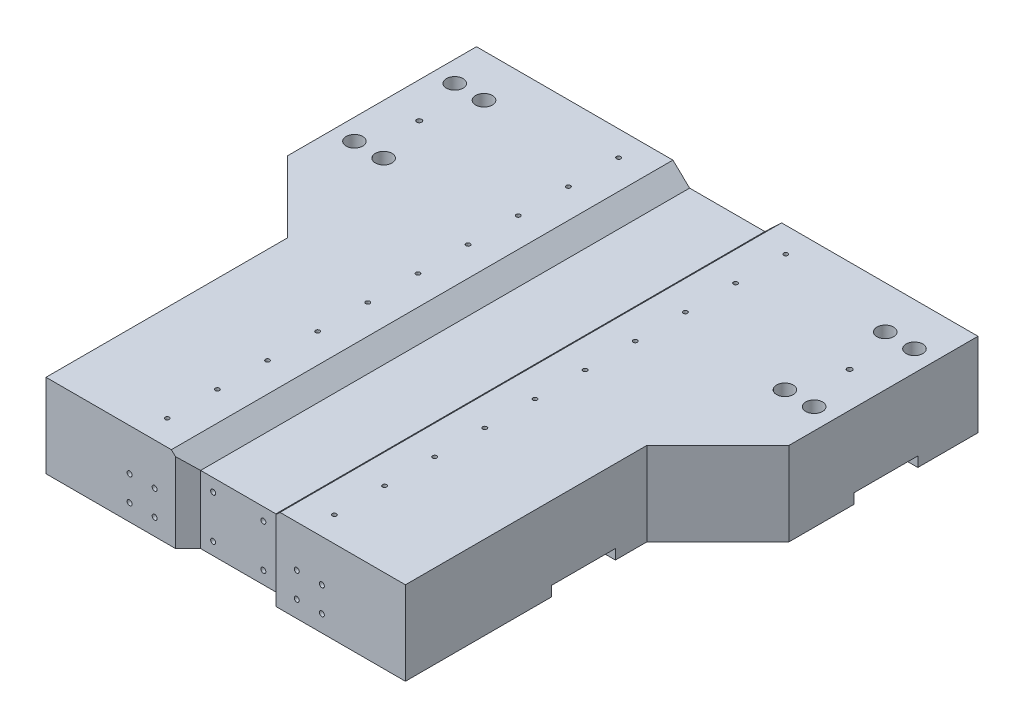
SolidWorks part; units mm, degrees
ref_plane "Front Plane" through (0, 0, 0) normal (0, 0, 1) x (1, 0, 0)
ref_plane "Top Plane" through (0, 0, 0) normal (0, 1, 0) x (1, 0, 0)
ref_plane "Right Plane" through (0, 0, 0) normal (1, 0, 0) x (0, 0, -1)
sketch "Sketch1" plane through (0, 0, 0) normal (0, 1, 0) x (1, 0, 0)
  line L1 (-300, 300) -> (300, 300)
  line L2 (-300, 300) -> (-300, -300)
  line L3 (-300, -300) -> (300, -300)
  line L4 (300, 300) -> (300, -300)
  line L5 (0, -300) -> (0, 300) construction
  line L6 (-300, 0) -> (300, 0) construction
  point P0 (0, 0)
  dimension "D1" = 600
extrude "Boss-Extrude1" add sketch "Sketch1" along normal blind 100
sketch "Sketch2" plane through (0, 100, 0) normal (0, 1, 0) x (1, 0, 0)
  line L0 (-300, -300) -> (-220, -300)
  line L9 (-300, -300) -> (300, -300) construction
  line L11 (300, -300) -> (220, -300)
  line L13 (-300, 300) -> (-300, -300) construction
  line L15 (-300, -300) -> (-300, 60)
  line L16 (300, -300) -> (300, 60)
  line L38 (-300, 60) -> (-300, 74)
  line L41 (300, 60) -> (300, 74)
  line L45 (-220, 74) -> (-300, 74)
  line L48 (220, 74) -> (300, 74)
  line L49 (-220, 74) -> (-215, 74)
  line L50 (-215, 74) -> (-215, -300)
  line L51 (-215, -300) -> (-220, -300)
  line L52 (220, 74) -> (215, 74)
  line L53 (215, 74) -> (215, -300)
  line L54 (215, -300) -> (220, -300)
extrude "Cut-Extrude1" cut sketch "Sketch2" against normal through all
chamfer "Chamfer5" distance 85 angle 45 2 edges at (-215, 50, -74) (215, 50, -74)
sketch "Sketch3" plane through (0, 0, 300) normal (0, 0, 1) x (1, 0, 0)
  line L0 (-35, 81) -> (-45, 81)
  line L2 (35, 81) -> (45, 81)
  line L4 (0, 81) -> (35, 81)
  line L8 (0, 81) -> (-35, 81)
  line L10 (-45, 100) -> (45, 100)
  line L13 (-215, 100) -> (215, 100) construction
  line L14 (-65, 100) -> (-45, 100)
  line L17 (45, 100) -> (65, 100)
  line L22 (-45, 81) -> (-65, 100)
  line L23 (45, 81) -> (65, 100)
extrude "Cut-Extrude2" cut sketch "Sketch3" against normal through all
sketch "Sketch9" plane through (0, 100, 0) normal (0, 1, 0) x (1, 0, 0)
  circle A0 centre (275, 129) radius 10
  circle A1 centre (240, 129) radius 10
  circle A3 centre (240, 249) radius 10
  circle A5 centre (275, 249) radius 10
  circle A6 centre (-275, 129) radius 10
  circle A7 centre (-240, 249) radius 10
  circle A8 centre (-275, 249) radius 10
  circle A11 centre (-240, 129) radius 10
  circle A12 centre (240, 189) radius 10 [skipped]
  circle A13 centre (275, 189) radius 10 [skipped]
  dimension "D1" = 2
  dimension "D2" = 3
extrude "Cut-Extrude5" cut sketch "Sketch9" against normal through all
sketch "Sketch12" plane through (0, 100, 0) normal (0, 1, 0) x (1, 0, 0)
  circle A40 centre (-100, -270) radius 2.5
  circle A41 centre (100, -270) radius 2.5
  circle A42 centre (100, -210) radius 2.5
  circle A43 centre (100, -150) radius 2.5
  circle A44 centre (100, -90) radius 2.5
  circle A45 centre (100, -30) radius 2.5
  circle A46 centre (100, 30) radius 2.5
  circle A47 centre (100, 90) radius 2.5
  circle A48 centre (100, 150) radius 2.5
  circle A49 centre (100, 210) radius 2.5
  circle A50 centre (100, 270) radius 2.5
  circle A61 centre (-100, -210) radius 2.5
  circle A62 centre (-100, -150) radius 2.5
  circle A63 centre (-100, -90) radius 2.5
  circle A64 centre (-100, -30) radius 2.5
  circle A65 centre (-100, 30) radius 2.5
  circle A66 centre (-100, 90) radius 2.5
  circle A67 centre (-100, 150) radius 2.5
  circle A68 centre (-100, 210) radius 2.5
  circle A69 centre (-100, 270) radius 2.5
  dimension "D1" = 2
  dimension "D2" = 10
extrude "Cut-Extrude7" cut sketch "Sketch12" against normal blind 30
sketch "Sketch14" plane through (0, 81, 0) normal (0, 1, 0) x (1, 0, 0)
  line L5 (-45, -300) -> (45, -300)
  line L6 (-45, -300) -> (-45, -285)
  line L11 (45, -285) -> (45, -300)
  line L15 (-45, -285) -> (45, -285)
extrude "Cut-Extrude8" cut sketch "Sketch14" against normal through all
chamfer "Chamfer3" distance 15 angle 45 2 edges at (45, 40.5, 300) (-45, 40.5, 300)
sketch "Sketch15" plane through (-300, 0, 0) normal (-1, 0, 0) x (0, 0, 1)
  line L0 (125, -0.7) -> (125, 12) construction
  line L1 (125, 12) -> (48.8, 12) construction
  line L2 (48.8, 12) -> (48.8, -0.7) construction
  line L3 (48.8, -0.7) -> (125, -0.7) construction
  line L4 (-228, 12) -> (-228, -0.7) construction
  line L5 (-228, -0.7) -> (-151.8, -0.7) construction
  line L6 (-151.8, -0.7) -> (-151.8, 12) construction
  line L7 (-151.8, 12) -> (-228, 12) construction
  line L8 (125, -0.7) -> (125, 12)
  line L9 (125, 12) -> (48.8, 12)
  line L10 (48.8, 12) -> (48.8, -0.7)
  line L11 (48.8, -0.7) -> (125, -0.7)
  line L12 (-228, 12) -> (-228, -0.7)
  line L13 (-228, -0.7) -> (-151.8, -0.7)
  line L14 (-151.8, -0.7) -> (-151.8, 12)
  line L15 (-151.8, 12) -> (-228, 12)
extrude "Cut-Extrude9" cut sketch "Sketch15" against normal through all
sketch "Sketch22" plane through (0, 0, -300) normal (0, 0, -1) x (-1, 0, 0)
  line L0 (-45, 81) -> (-45, 0)
  line L1 (-300, 0) -> (300, 0) construction
  line L2 (-45, 0) -> (45, 0)
  line L3 (45, 0) -> (45, 81)
  line L4 (45, 81) -> (-45, 81)
sketch "Sketch17" plane through (0, 0, 285) normal (0, 0, 1) x (1, 0, 0)
  line L8 (30, 66) -> (-30, 66)
  line L9 (-30, 66) -> (-30, 15)
  line L10 (-30, 15) -> (30, 15)
  line L11 (30, 15) -> (30, 66)
  line L12 (30, 66) -> (-30, 66)
  line L13 (-30, 66) -> (-30, 15)
  line L14 (-30, 15) -> (30, 15)
  line L15 (30, 15) -> (30, 66)
  dimension "D1" = 15
sketch "Sketch19" plane through (0, 0, -300) normal (0, 0, -1) x (-1, 0, 0)
  line L0 (30, 66) -> (30, 15) construction
  line L1 (30, 15) -> (-30, 15) construction
  line L2 (-30, 15) -> (-30, 66) construction
  line L3 (-30, 66) -> (30, 66) construction
  line L4 (30, 66) -> (30, 15)
  line L5 (30, 15) -> (-30, 15)
  line L6 (-30, 15) -> (-30, 66)
  line L7 (-30, 66) -> (30, 66)
sketch "Sketch20" plane through (0, 0, 300) normal (0, 0, 1) x (1, 0, 0)
  line L2 (85, 100) -> (85, 50)
  line L3 (-85, 0) -> (-85, 20)
  line L4 (-215, 100) -> (-65, 100) construction
  line L5 (-85, 100) -> (-85, 50)
  line L6 (115, 100) -> (115, 50)
  line L7 (-115, 100) -> (-115, 50)
  line L8 (0, 34.1921) -> (0, 91.6213)
  line L9 (-215, 0) -> (-60, 0) construction
  line L10 (-115, 0) -> (-115, 20)
  line L11 (85, 0) -> (85, 20)
  line L12 (115, 0) -> (115, 20)
sketch "Sketch21" plane through (0, 0, -300) normal (0, 0, -1) x (-1, 0, 0)
  line L4 (-115, 100) -> (-115, 80)
  line L5 (-85, 100) -> (-85, 80)
  line L6 (85, 100) -> (85, 80)
  line L7 (115, 100) -> (115, 80)
  line L8 (115, 0) -> (115, 20) construction
  line L9 (85, 0) -> (85, 20) construction
  line L10 (-85, 0) -> (-85, 20) construction
  line L11 (-115, 0) -> (-115, 20) construction
  line L12 (115, 0) -> (115, 20)
  line L13 (85, 0) -> (85, 20)
  line L14 (-85, 0) -> (-85, 20)
  line L15 (-115, 0) -> (-115, 20)
hole_wizard "Ø6.0mm Dowel Hole1" positions "3DSketch2" profile "Sketch18" hole size "Ø6.0" standard "ANSI Metric"
sketch3d "3DSketch2"
  point P0 (-30, 66, 285)
  point P3 (30, 66, 285)
  point P6 (30, 15, 285)
  point P9 (-30, 15, 285)
  point P13 (30, 66, -300)
  point P16 (-30, 66, -300)
  point P19 (-30, 15, -300)
  point P22 (30, 15, -300)
  point P26 (-85, 50, 300)
  point P29 (-115, 50, 300)
  point P32 (85, 50, 300)
  point P35 (115, 50, 300)
  point P38 (-115, 80, -300)
  point P41 (-85, 80, -300)
  point P44 (85, 80, -300)
  point P47 (115, 80, -300)
  point P50 (-115, 20, 300)
  point P53 (-85, 20, 300)
  point P56 (85, 20, 300)
  point P59 (115, 20, 300)
  point P62 (-115, 20, -300)
  point P65 (-85, 20, -300)
  point P68 (85, 20, -300)
  point P71 (115, 20, -300)
sketch "Sketch18" plane through (-30, 66, 285) normal (1, 0, 0) x (0, -1, 0)
  line L0 (0, 0) -> (0, 31.8026)
  line L1 (0, 31.8026) -> (3, 30)
  line L2 (3, 30) -> (3, 0)
  line L5 (3, 0) -> (0, 0)
  line L10 (0, 31.8026) -> (-3, 30) construction
  line L11 (0, -6.35) -> (0, 107.95) construction
  dimension "Hole Dia." = 6
  dimension "Hole Depth" = 30
  dimension "Drill Angle" = 118
sketch "Sketch23" plane through (0, 100, 0) normal (0, 1, 0) x (1, 0, 0)
  circle A0 centre (-257.5, 189) radius 3
  circle A1 centre (257.5, 189) radius 3
extrude "Cut-Extrude10" cut sketch "Sketch23" against normal through all
